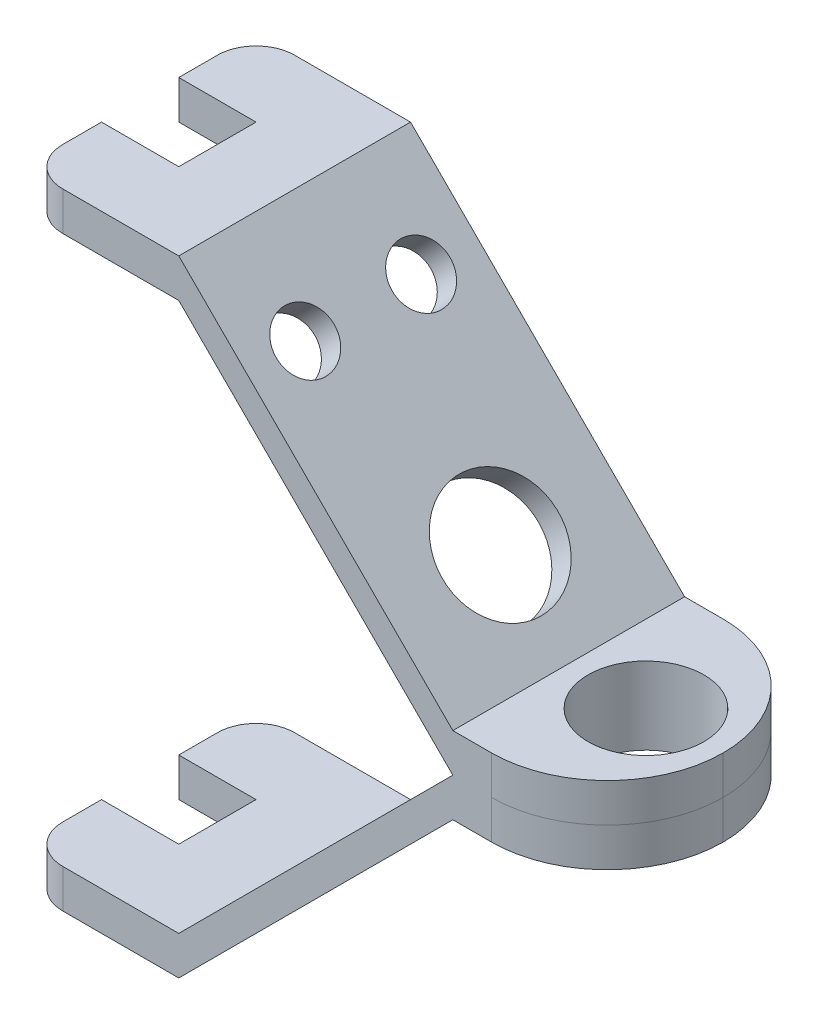
SolidWorks part; units mm, degrees
ref_plane "Alzado" through (0, 0, 0) normal (0, 0, 1) x (1, 0, 0)
ref_plane "Planta" through (0, 0, 0) normal (0, 1, 0) x (1, 0, 0)
ref_plane "Vista lateral" through (0, 0, 0) normal (1, 0, 0) x (0, 0, -1)
sketch "Croquis2" plane through (0, 0, 0) normal (0, 0, 1) x (1, 0, 0)
  line L0 (-36.1801, 22.9071) -> (3.8199, 22.9071)
  line L1 (-36.1801, 22.9071) -> (-36.1801, 32.9071)
  line L2 (-36.1801, 32.9071) -> (3.8199, 32.9071)
  line L3 (3.8199, 22.9071) -> (74.7678, -48.0408)
  line L4 (3.8199, 32.9071) -> (74.7678, -38.0408)
  line L5 (74.7678, -38.0408) -> (114.7678, -38.0408)
  line L6 (114.7678, -38.0408) -> (114.7678, -48.0408)
  line L7 (114.7678, -48.0408) -> (74.7678, -48.0408)
  dimension "D1" = 225
  dimension "D2" = 40
  dimension "D3" = 40
  dimension "D4" = 10
  dimension "D5" = 40
  dimension "D6" = 40
  dimension "D7" = 225
extrude "Saliente-Extruir1" add sketch "Croquis2" along normal blind 60
sketch "Croquis3" plane through (0, 0, 0) normal (0, 1, 0) x (1, 0, 0)
  line L0 (-36.1801, -60) -> (-36.1801, 0) construction
  line L1 (-56.1801, -40) -> (-16.1801, -40)
  line L2 (-56.1801, -40) -> (-56.1801, -20)
  line L3 (-56.1801, -20) -> (-16.1801, -20)
  line L4 (-16.1801, -40) -> (-16.1801, -20)
  line L5 (-56.1801, -40) -> (-16.1801, -20) construction
  line L6 (-56.1801, -20) -> (-16.1801, -40) construction
  point P0 (-36.1801, -30)
extrude "Cortar-Extruir1" cut sketch "Croquis3" along normal blind 46
sketch "Croquis4" plane through (0, 0, 0) normal (0, 1, 0) x (1, 0, 0)
  circle A0 centre (94.7678, -30) radius 15
extrude "Cortar-Extruir5" cut sketch "Croquis4" against normal blind 57
sketch "Croquis12" plane through (18.3635, 18.3635, 0) normal (0.7071, 0.7071, 0) x (0, 0, -1)
  circle A0 centre (-15, -4.5161) radius 7.5
  circle A1 centre (-45, -4.5161) radius 7.5
  circle A2 centre (-30, -54.6839) radius 15
extrude "Cortar-Extruir6" cut sketch "Croquis12" against normal blind 19 and the other way blind 16
fillet "Redondeo2" radius 10 2 edges at (-36.1801, 27.9071, 0) (-36.1801, 27.9071, 60)
fillet "Redondeo3" radius 30 2 edges at (114.7678, -43.0408, 60) (114.7678, -43.0408, 0)
mirror "Simetría1" about plane through (114.7678, -48.0408, 60) normal (0, 1, 0) of "Saliente-Extruir1"
sketch "Croquis13" plane through (0, 0, 0) normal (0, 1, 0) x (1, 0, 0)
  circle A0 centre (94.7678, -30) radius 15
extrude "Cortar-Extruir7" cut sketch "Croquis13" against normal blind 82
fillet "Redondeo4" radius 30 2 edges at (114.7678, -53.0408, 60) (114.7678, -53.0408, 0)
sketch "Croquis14" plane through (0, 0, 0) normal (0, 1, 0) x (1, 0, 0)
  line L1 (-36.1801, -20) -> (-16.1801, -20)
  line L2 (-36.1801, -20) -> (-36.1801, -40)
  line L3 (-36.1801, -40) -> (-16.1801, -40)
  line L4 (-16.1801, -20) -> (-16.1801, -40)
extrude "Cortar-Extruir8" cut sketch "Croquis14" against normal blind 156
sketch "Croquis16" plane through (66.4043, -66.4043, 0) normal (0.7071, -0.7071, 0) x (0, 0, -1)
  circle A0 centre (-45, -63.4239) radius 7.5
  circle A1 centre (-15, -63.4239) radius 7.5
  circle A2 centre (-30, -13.2561) radius 15
extrude "Cortar-Extruir9" cut sketch "Croquis16" against normal blind 54 and the other way blind 37
fillet "Redondeo5" radius 10 2 edges at (-36.1801, -123.9888, 0) (-36.1801, -123.9888, 60)
